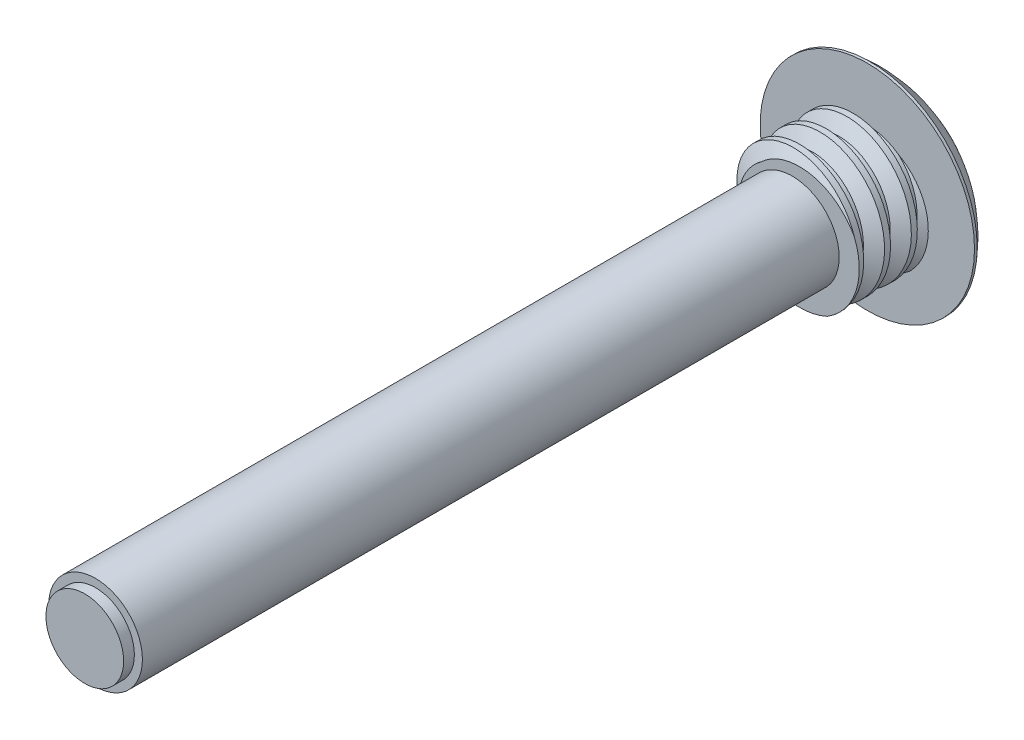
SolidWorks part; units mm, degrees
ref_plane "Front Plane" through (0, 0, 0) normal (0, 0, 1) x (1, 0, 0)
ref_plane "Top Plane" through (0, 0, 0) normal (0, 1, 0) x (1, 0, 0)
ref_plane "Right Plane" through (0, 0, 0) normal (1, 0, 0) x (0, 0, -1)
sketch "Sketch2" plane through (0, 0, 0) normal (0, 0, 1) x (1, 0, 0)
  circle A0 centre (0, 0) radius 3.175
curve "Helix/Spiral1" pitch 1.27 height 5.08 radius 3.175 left hand yes centre (0, 0, 0) axis (0, 0, 1) start towards (0, 1, 0)
sketch "Sketch3" plane through (0, 0, 0) normal (0, 0, 1) x (1, 0, 0)
  circle A0 centre (0, 0) radius 3.175
extrude "Boss-Extrude1" add sketch "Sketch3" along normal blind 3.556 contours A0
sketch "Sketch5" plane through (0, 0, 0) normal (1, 0, 0) x (0, 0, -1)
  line L0 (0.127, 2.54) -> (0.4936, 3.175)
  line L1 (0.4936, 3.175) -> (-0.4936, 3.175)
  line L2 (-0.4936, 3.175) -> (-0.127, 2.54)
  line L3 (-0.127, 2.54) -> (0.127, 2.54)
  line L4 (0, 3.175) -> (0, 2.54) construction
  dimension "D1" = 0.635
  dimension "D2" = 0.254
  dimension "D3" = 60
sweep "Cut-Sweep1" cut profiles "Sketch5" path "Helix/Spiral1" align with end faces yes
sketch "Sketch10" plane through (0, 0, 3.556) normal (0, 0, 1) x (1, 0, 0)
  circle A0 centre (0, 0) radius 2.2225
  dimension "D1" = 4.445
extrude "Boss-Extrude5" add sketch "Sketch10" along normal blind 33.02
sketch "Sketch9" plane through (0, 0, 0) normal (0, 0, 1) x (1, 0, 0)
  circle A0 centre (0, 0) radius 5.08
  dimension "D1" = 10.16
extrude "Boss-Extrude4" add sketch "Sketch9" against normal blind 0.127
dome "Dome3" faces to dome 1 distance 2.38 reverse direction no elliptical dome no face at (5.08, 0, -0.127) parameters "D1"=2.38
sketch "Sketch11" plane through (0, 0, 36.576) normal (0, 0, 1) x (1, 0, 0)
  circle A0 centre (0, 0) radius 1.8415
  dimension "D1" = 3.683
extrude "Boss-Extrude6" add sketch "Sketch11" along normal blind 0.508
